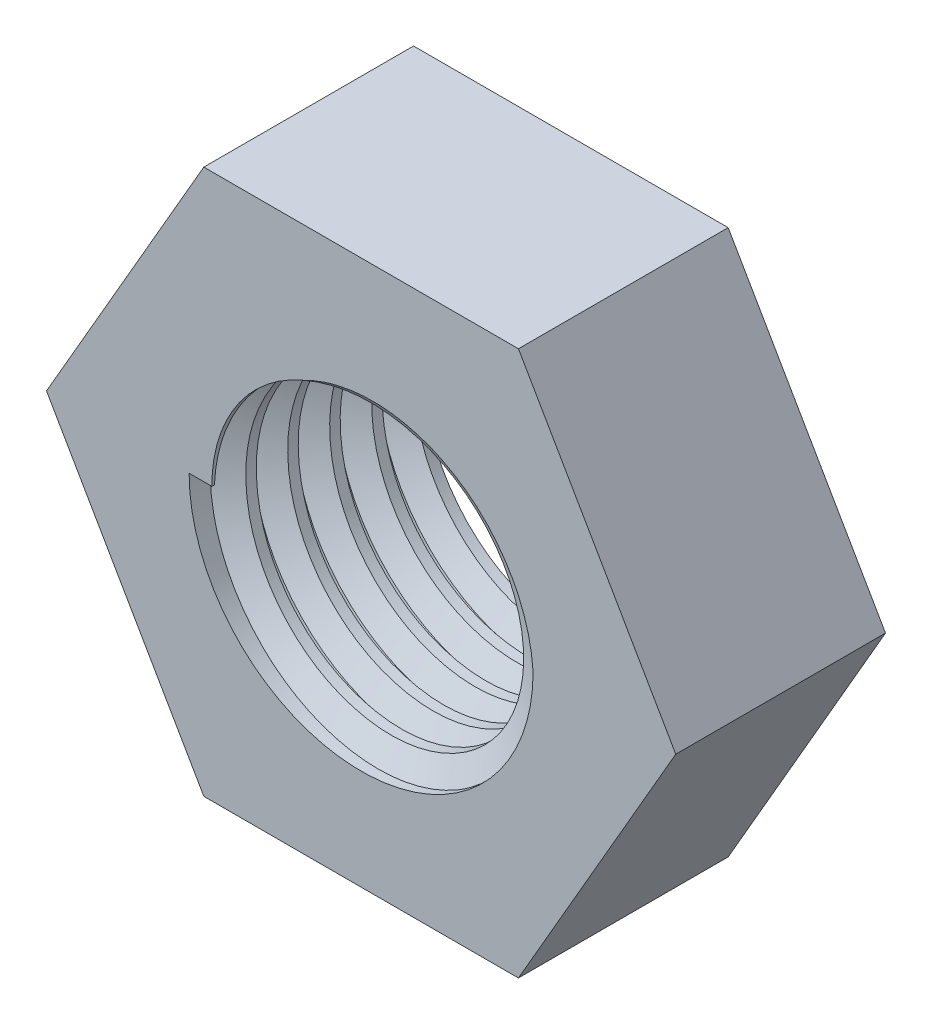
SolidWorks part; units mm, degrees
ref_plane "Alzado" through (0, 0, 0) normal (0, 0, 1) x (1, 0, 0)
ref_plane "Planta" through (0, 0, 0) normal (0, 1, 0) x (1, 0, 0)
ref_plane "Vista lateral" through (0, 0, 0) normal (1, 0, 0) x (0, 0, -1)
sketch "Croquis1" plane through (0, 0, 0) normal (0, 0, 1) x (1, 0, 0)
  circle A0 centre (0, 0) radius 8.2
  circle A1 centre (0, 0) radius 15
extrude "Saliente-Extruir1" add sketch "Croquis1" along normal blind 10
thread "Rosca1" pitch 2 method extrude profile "Perfil de rosca1" start angle 0, offset 1, length 10, pitch 2, diameter 16.4
ref_plane "Plano1" through (-8.2, 0, 11) normal (0, -1, 0) x (-1, 0, 0)
sketch "Perfil de rosca1" plane through (-8.2, 0, 11) normal (0, -1, 0) x (-1, 0, 0)
  line L0 (0, 0) -> (0, 2) construction
  line L11 (0, 0) -> (0, 1.75)
  line L12 (0, 1.75) -> (-1.0825, 1.125)
  line L13 (-1.0825, 1.125) -> (-1.0825, 0.625)
  line L15 (-1.0825, 0.625) -> (0, 0)
  line L17 (-1.0825, 0.875) -> (0, 0.875) construction
  point P2 (0, 0)
  dimension "Pitch" = 2
  dimension "Profile_Angle" = 60
  dimension "Profile_Land" = 0.5
  dimension "Profile_Height" = 1.0825
sketch "Croquis4" plane through (0, 0, 0) normal (0, 1, 0) x (1, 0, 0)
  line L1 (15, -10) -> (-15, -10)
  line L2 (15, -10) -> (15, 0)
  line L3 (15, 0) -> (-15, 0)
  line L4 (-15, -10) -> (-15, 0)
  line L5 (16.8986, -12.2257) -> (-17.9902, -12.2257)
  line L6 (16.8986, -12.2257) -> (16.8986, 2.97)
  line L7 (16.8986, 2.97) -> (-17.9902, 2.97)
  line L8 (-17.9902, -12.2257) -> (-17.9902, 2.97)
extrude "Cortar-Extruir1" cut sketch "Croquis4" against normal blind 17
sketch "Croquis5" plane through (0, 0, 0) normal (0, 1, 0) x (1, 0, 0)
  line L1 (-15, -10) -> (15, -10)
  line L2 (-15, -10) -> (-15, 0)
  line L3 (-15, 0) -> (15, 0)
  line L4 (15, -10) -> (15, 0)
  line L5 (-19.0806, -12.254) -> (19.7407, -12.254)
  line L6 (-19.0806, -12.254) -> (-19.0806, 3.7944)
  line L7 (-19.0806, 3.7944) -> (19.7407, 3.7944)
  line L8 (19.7407, -12.254) -> (19.7407, 3.7944)
extrude "Cortar-Extruir2" cut sketch "Croquis5" along normal blind 17
sketch "Croquis6" plane through (0, 0, 10) normal (0, 0, 1) x (1, 0, 0)
  line L1 (-15, 0) -> (-7.5, -12.9904)
  line L2 (-7.5, -12.9904) -> (7.5, -12.9904)
  line L3 (7.5, -12.9904) -> (15, 0)
  line L4 (15, 0) -> (7.5, 12.9904)
  line L5 (7.5, 12.9904) -> (-7.5, 12.9904)
  line L6 (-7.5, 12.9904) -> (-15, 0)
  circle A1 centre (0, 0) radius 16.8138
extrude "Cortar-Extruir3" cut sketch "Croquis6" against normal blind 17
